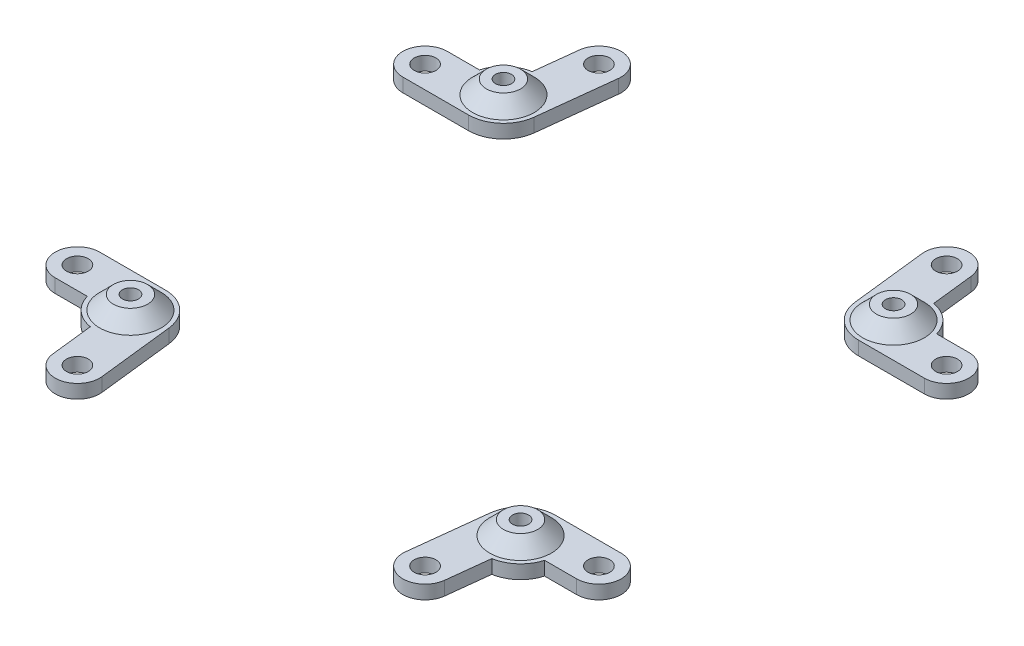
SolidWorks part; units mm, degrees
ref_plane "Front Plane" through (0, 0, 0) normal (0, 0, 1) x (1, 0, 0)
ref_plane "Top Plane" through (0, 0, 0) normal (0, 1, 0) x (1, 0, 0)
ref_plane "Right Plane" through (0, 0, 0) normal (1, 0, 0) x (0, 0, -1)
sketch "Sketch1" plane through (0, 0, 0) normal (0, 1, 0) x (1, 0, 0)
  line L0 (-76.2, -76.2) -> (0, -76.2) construction
  line L1 (0, -76.2) -> (0, 0) construction
  line L2 (0, 0) -> (-76.2, 0) construction
  line L3 (-76.2, 0) -> (-76.2, -76.2) construction
  circle A1 centre (-76.2, -76.2) radius 3.175
  circle A2 centre (-50.8, -76.2) radius 3.175
  circle A3 centre (-25.4, -76.2) radius 3.175
  circle A4 centre (0, -76.2) radius 3.175
  circle A5 centre (25.4, -76.2) radius 3.175
  circle A6 centre (50.8, -76.2) radius 3.175
  circle A7 centre (76.2, -76.2) radius 3.175
  circle A8 centre (-50.8, -50.8) radius 3.175
  circle A9 centre (-25.4, -50.8) radius 3.175
  circle A10 centre (0, -50.8) radius 3.175
  circle A11 centre (25.4, -50.8) radius 3.175
  circle A12 centre (50.8, -50.8) radius 3.175
  circle A13 centre (76.2, -50.8) radius 3.175
  circle A14 centre (-50.8, -25.4) radius 3.175
  circle A15 centre (-25.4, -25.4) radius 3.175
  circle A16 centre (0, -25.4) radius 3.175
  circle A17 centre (25.4, -25.4) radius 3.175
  circle A18 centre (50.8, -25.4) radius 3.175
  circle A19 centre (76.2, -25.4) radius 3.175
  circle A20 centre (-50.8, 0) radius 3.175
  circle A21 centre (-25.4, 0) radius 3.175
  circle A22 centre (0, 0) radius 3.175
  circle A23 centre (25.4, 0) radius 3.175
  circle A24 centre (50.8, 0) radius 3.175
  circle A25 centre (76.2, 0) radius 3.175
  circle A26 centre (-50.8, 25.4) radius 3.175
  circle A27 centre (-25.4, 25.4) radius 3.175
  circle A28 centre (0, 25.4) radius 3.175
  circle A29 centre (25.4, 25.4) radius 3.175
  circle A30 centre (50.8, 25.4) radius 3.175
  circle A31 centre (76.2, 25.4) radius 3.175
  circle A32 centre (-50.8, 50.8) radius 3.175
  circle A33 centre (-25.4, 50.8) radius 3.175
  circle A34 centre (0, 50.8) radius 3.175
  circle A35 centre (25.4, 50.8) radius 3.175
  circle A36 centre (50.8, 50.8) radius 3.175
  circle A37 centre (76.2, 50.8) radius 3.175
  circle A38 centre (-50.8, 76.2) radius 3.175
  circle A39 centre (-25.4, 76.2) radius 3.175
  circle A40 centre (0, 76.2) radius 3.175
  circle A41 centre (25.4, 76.2) radius 3.175
  circle A42 centre (50.8, 76.2) radius 3.175
  circle A43 centre (76.2, 76.2) radius 3.175
  circle A44 centre (-76.2, -50.8) radius 3.175
  circle A45 centre (-76.2, -25.4) radius 3.175
  circle A46 centre (-76.2, 0) radius 3.175
  circle A47 centre (-76.2, 25.4) radius 3.175
  circle A48 centre (-76.2, 50.8) radius 3.175
  circle A49 centre (-76.2, 76.2) radius 3.175
  point P3 (-15.8043, -15.8043)
  point P5 (0, 0)
  dimension "D1" = 6.35
  dimension "D2" = 76.2
  dimension "D3" = 7
  dimension "D4" = 7
sketch "Sketch2" plane through (0, 0, 0) normal (0, 1, 0) x (1, 0, 0)
  line L1 (-57, -54.5) -> (57, -54.5) construction
  line L2 (-57, -54.5) -> (-57, 54.5) construction
  line L3 (-57, 54.5) -> (57, 54.5) construction
  line L4 (57, -54.5) -> (57, 54.5) construction
  line L5 (-57, -54.5) -> (57, 54.5) construction
  line L6 (-57, 54.5) -> (57, -54.5) construction
  line L7 (-65, -62.5) -> (65, -62.5)
  line L8 (-65, -62.5) -> (-65, 62.5)
  line L9 (-65, 62.5) -> (65, 62.5)
  line L10 (65, -62.5) -> (65, 62.5)
  line L11 (-65, -62.5) -> (65, 62.5) construction
  line L12 (-65, 62.5) -> (65, -62.5) construction
  circle A0 centre (-57, 54.5) radius 1.75
  circle A1 centre (57, 54.5) radius 1.75
  circle A2 centre (57, -54.5) radius 1.75
  circle A3 centre (-57, -54.5) radius 1.75
  point P0 (0, 0)
  point P10 (0, 0)
  dimension "D3" = 3.5
  dimension "D1" = 114
  dimension "D2" = 109
  dimension "D4" = 130
  dimension "D5" = 125
sketch "Sketch3" plane through (0, 0, 0) normal (0, 1, 0) x (1, 0, 0)
  line L1 (-66.8082, 57.3) -> (-76.2, 57.3)
  line L2 (-76.2, 44.3) -> (-57, 44.3)
  line L5 (-44.3419, 75.4631) -> (-46.8658, 53.3437)
  line L6 (-57.2581, 76.9369) -> (-58.67, 64.5624)
  arc A0 (-76.2, 57.3) -> (-76.2, 44.3) centre (-76.2, 50.8) ccw
  arc A1 (-44.3419, 75.4631) -> (-57.2581, 76.9369) centre (-50.8, 76.2) ccw
  circle A3 centre (-57, 54.5) radius 2.35
  circle A4 centre (-50.8, 76.2) radius 3.175
  circle A5 centre (-76.2, 50.8) radius 3.175
  arc A6 (-57, 44.3) -> (-46.8658, 53.3437) centre (-57, 54.5) ccw
  arc A7 (-58.67, 64.5624) -> (-66.8082, 57.3) centre (-57, 54.5) ccw
  dimension "D1" = 4.7
  dimension "D2" = 6.35
  dimension "D3" = 6.5
extrude "Boss-Extrude1" add sketch "Sketch3" along normal blind 4
sketch "Sketch4" plane through (0, 4, 0) normal (0, 1, 0) x (1, 0, 0)
  circle A0 centre (-57, 54.5) radius 5
  circle A1 centre (-57, 54.5) radius 2.35 construction
  circle A2 centre (-57, 54.5) radius 2.35
  dimension "D1" = 10
extrude "Boss-Extrude2" add sketch "Sketch4" along normal blind 4
chamfer "Chamfer1" distance 4 angle 45 1 edges at (-57, 4, -49.5)
mirror "Mirror2" about plane through (0, 0, 0) normal (1, 0, 0) of bodies 102
mirror "Mirror3" about plane through (0, 0, 0) normal (0, 0, 1) of bodies 102 103
